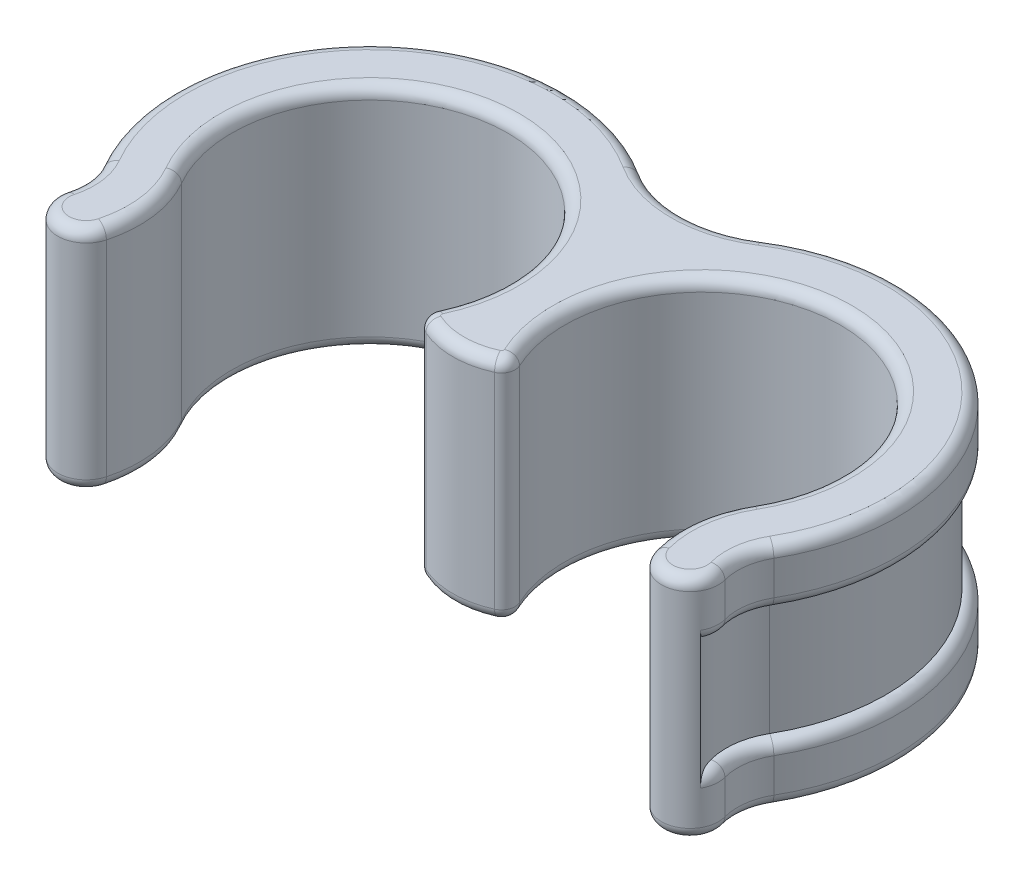
SolidWorks part; units mm, degrees
ref_plane "Front Plane" through (0, 0, 0) normal (0, 0, 1) x (1, 0, 0)
ref_plane "Top Plane" through (0, 0, 0) normal (0, 1, 0) x (1, 0, 0)
ref_plane "Right Plane" through (0, 0, 0) normal (1, 0, 0) x (0, 0, -1)
sketch "Sketch1" plane through (0, 0, 0) normal (0, 1, 0) x (1, 0, 0)
  line L0 (0, 0) -> (15249.8631, 0) construction
  line L1 (0, 0) -> (0, 15249.8631) construction
  line L2 (9.271, 0) -> (2.6169, -3.8417) construction
  line L3 (9.271, 0) -> (18.6747, -5.4293) construction
  line L4 (-21.4244, -7.0168) -> (-18.6747, -5.4293) construction
  line L5 (-21.4244, -7.0168) -> (-18.3576, -7.8385) construction
  circle A0 centre (-9.271, 0) radius 7.6835 construction
  circle A1 centre (9.271, 0) radius 7.6835 construction
  arc A2 (15.9251, -3.8418) -> (2.2951, -3.2208) centre (9.271, 0) ccw
  arc A3 (-2.2951, -3.2208) -> (-15.9251, -3.8418) centre (-9.271, 0) ccw
  arc A4 (-1.9177, -4.2343) -> (1.9177, -4.2343) centre (0, 0) ccw
  arc A5 (3.421, 9.1479) -> (18.6747, -5.4293) centre (9.271, 0) cw
  arc A6 (3.421, 9.1479) -> (-3.421, 9.1479) centre (0, 14.4976) cw
  arc A7 (-3.421, 9.1479) -> (-18.6747, -5.4293) centre (-9.271, 0) ccw
  arc A8 (-18.6747, -5.4293) -> (-18.3576, -7.8385) centre (-21.4244, -7.0168) cw
  arc A9 (-18.3576, -7.8385) -> (-15.2907, -8.6603) centre (-16.8241, -8.2494) ccw
  arc A10 (-15.2907, -8.6603) -> (-15.9251, -3.8418) centre (-21.4244, -7.0168) ccw
  arc A11 (18.6747, -5.4293) -> (18.3576, -7.8385) centre (21.4244, -7.0168) ccw
  arc A12 (18.3576, -7.8385) -> (15.2907, -8.6603) centre (16.8241, -8.2494) cw
  arc A13 (15.2907, -8.6603) -> (15.9251, -3.8418) centre (21.4244, -7.0168) cw
  arc A14 (1.9177, -4.2343) -> (2.2951, -3.2208) centre (1.6033, -3.5402) ccw
  arc A15 (-1.9177, -4.2343) -> (-2.2951, -3.2208) centre (-1.6033, -3.5402) cw
  point P7 (-1.5875, 0)
  point P10 (1.5875, 0)
  dimension "D1" = 15.367
  dimension "D3" = 30
  dimension "D4" = 30
  dimension "D5" = 0.762
  dimension "D6" = 3.175
  dimension "D7" = 6.35
  dimension "D9" = 6.35
  dimension "D2" = 3.175
  dimension "D8" = 45
extrude "Boss-Extrude1" add sketch "Sketch1" along normal mid plane 12.7
fillet "Fillet1" radius 0.635 28 edges at (18.2765, -6.35, 6.6023) (17.235, -6.35, 9.7828) (15.1287, -6.35, 6.1879) (9.6207, -6.35, -7.6755) (2.3174, -6.35, 3.8061) (0, -6.35, 4.6484) (-2.3174, -6.35, 3.8061) (-9.6207, -6.35, -7.6755) (-15.1287, -6.35, 6.1879) (-17.235, -6.35, 9.7828) (-18.2765, -6.35, 6.6023) (-16.7731, -6.35, -7.8502) (0, -6.35, -8.1476) (18.2765, 6.35, 6.6023) (17.235, 6.35, 9.7828) (15.1287, 6.35, 6.1879) (9.6207, 6.35, -7.6755) (2.3174, 6.35, 3.8061) (0, 6.35, 4.6484) (-2.3174, 6.35, 3.8061) (-9.6207, 6.35, -7.6755) (-15.1287, 6.35, 6.1879) (-17.235, 6.35, 9.7828) (-18.2765, 6.35, 6.6023) (-16.7731, 6.35, -7.8502) (0, 6.35, -8.1476) (16.7731, -6.35, -7.8502) (16.7731, 6.35, -7.8502)
sketch "Sketch2" plane through (0, 0, 0) normal (0, 1, 0) x (1, 0, 0)
  arc A0 (-18.1985, -9.044) -> (-18.1248, -5.1118) centre (-21.4244, -7.0168) ccw
  arc A1 (-3.7631, 8.613) -> (-18.1248, -5.1118) centre (-9.271, 0) ccw
  arc A2 (-3.7631, 8.613) -> (3.7631, 8.613) centre (0, 14.4976) ccw
  arc A3 (18.1248, -5.1118) -> (3.7631, 8.613) centre (9.271, 0) ccw
  arc A4 (18.1248, -5.1118) -> (18.1985, -9.044) centre (21.4244, -7.0168) ccw
  arc A5 (15.2907, -8.6603) -> (18.3576, -7.8385) centre (16.8241, -8.2494) ccw construction
  arc A6 (-18.3576, -7.8385) -> (-15.2907, -8.6603) centre (-16.8241, -8.2494) ccw construction
  arc A7 (18.1985, -9.044) -> (18.3576, -7.8385) centre (16.8241, -8.2494) ccw
  arc A8 (-18.3576, -7.8385) -> (-18.1985, -9.044) centre (-16.8241, -8.2494) ccw
  arc A9 (-17.7442, -8.0029) -> (-18.1248, -5.1118) centre (-21.4244, -7.0168) ccw construction
  arc A10 (18.1248, -5.1118) -> (17.7442, -8.0029) centre (21.4244, -7.0168) ccw construction
  arc A14 (15.9251, -3.8418) -> (2.2951, -3.2208) centre (9.271, 0) ccw
  arc A15 (15.9251, -3.8418) -> (15.2907, -8.6603) centre (21.4244, -7.0168) ccw
  arc A16 (15.2907, -8.6603) -> (18.3576, -7.8385) centre (16.8241, -8.2494) ccw
  arc A17 (18.6747, -5.4293) -> (18.3576, -7.8385) centre (21.4244, -7.0168) ccw
  arc A18 (18.6747, -5.4293) -> (3.421, 9.1479) centre (9.271, 0) ccw
  arc A19 (-3.421, 9.1479) -> (3.421, 9.1479) centre (0, 14.4976) ccw
  arc A20 (-3.421, 9.1479) -> (-18.6747, -5.4293) centre (-9.271, 0) ccw
  arc A21 (-18.3576, -7.8385) -> (-18.6747, -5.4293) centre (-21.4244, -7.0168) ccw
  arc A22 (-18.3576, -7.8385) -> (-15.2907, -8.6603) centre (-16.8241, -8.2494) ccw
  arc A23 (-15.2907, -8.6603) -> (-15.9251, -3.8418) centre (-21.4244, -7.0168) ccw
  arc A24 (-2.2951, -3.2208) -> (-15.9251, -3.8418) centre (-9.271, 0) ccw
  arc A25 (-2.2951, -3.2208) -> (-1.9177, -4.2343) centre (-1.6033, -3.5402) ccw
  arc A26 (-1.9177, -4.2343) -> (1.9177, -4.2343) centre (0, 0) ccw
  arc A27 (1.9177, -4.2343) -> (2.2951, -3.2208) centre (1.6033, -3.5402) ccw
  arc A31 (18.6747, -5.4293) -> (18.3576, -7.8385) centre (21.4244, -7.0168) ccw
  arc A32 (18.6747, -5.4293) -> (3.421, 9.1479) centre (9.271, 0) ccw
  arc A33 (-3.421, 9.1479) -> (3.421, 9.1479) centre (0, 14.4976) ccw
  arc A34 (-3.421, 9.1479) -> (-18.6747, -5.4293) centre (-9.271, 0) ccw
  arc A35 (-18.3576, -7.8385) -> (-18.6747, -5.4293) centre (-21.4244, -7.0168) ccw
  dimension "D1" = 0
  dimension "D2" = 0.635
extrude "Cut-Extrude1" cut sketch "Sketch2" against normal mid plane 6.35
fillet "Fillet2" radius 0.635 14 edges at (18.398, 3.175, 8.4571) (18.2765, 3.175, 6.6023) (-18.398, 3.175, 8.4571) (-18.2765, 3.175, 6.6023) (-16.7731, 3.175, -7.8502) (0, 3.175, -8.1476) (18.398, -3.175, 8.4571) (18.2765, -3.175, 6.6023) (-18.398, -3.175, 8.4571) (-18.2765, -3.175, 6.6023) (-16.7731, -3.175, -7.8502) (0, -3.175, -8.1476) (16.7731, 3.175, -7.8502) (16.7731, -3.175, -7.8502)
